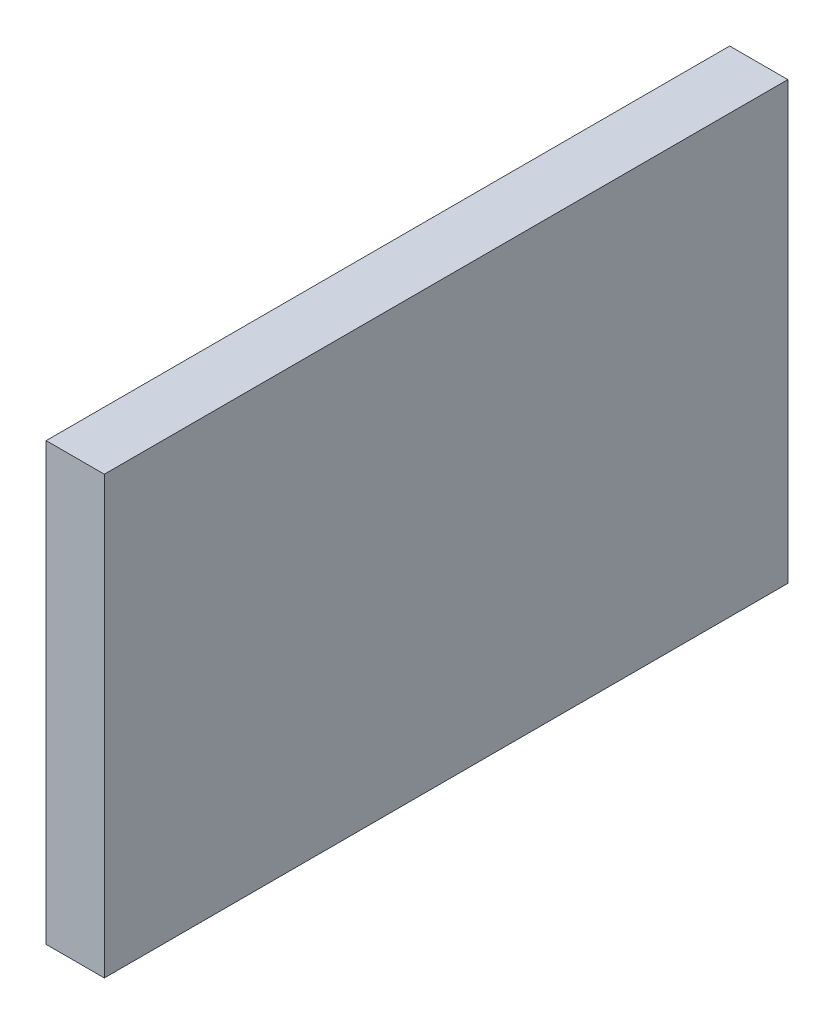
SolidWorks part; units mm, degrees
material "Acrylic (Medium-high impact)"
ref_plane "Front Plane" through (0, 0, 0) normal (0, 0, 1) x (1, 0, 0)
ref_plane "Top Plane" through (0, 0, 0) normal (0, 1, 0) x (1, 0, 0)
ref_plane "Right Plane" through (0, 0, 0) normal (1, 0, 0) x (0, 0, -1)
sketch "Sketch1" plane through (0, 0, 39.2805) normal (0, 0, 1) x (1, 0, 0)
  line L0 (13.9215, 24.6718) -> (8.9215, 24.6718) construction
  line L1 (8.9215, 47.1718) -> (11.9215, 47.1718)
  line L2 (8.9215, 47.1718) -> (8.9215, 24.6718)
  line L3 (8.9215, 24.6718) -> (11.9215, 24.6718)
  line L4 (11.9215, 47.1718) -> (11.9215, 24.6718)
  dimension "D1" = 3
extrude "Boss-Extrude1" add sketch "Sketch1" along normal up to surface (35.25 mm away)
